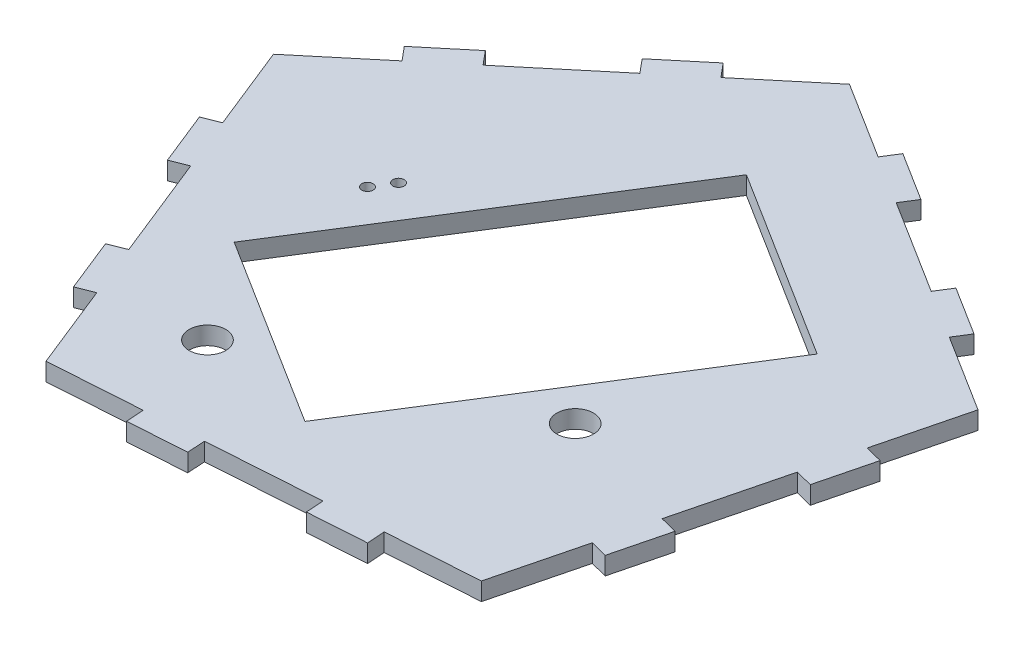
SolidWorks part; units mm, degrees
ref_plane "Front Plane" through (0, 0, 0) normal (0, 0, 1) x (1, 0, 0)
ref_plane "Top Plane" through (0, 0, 0) normal (0, 1, 0) x (1, 0, 0)
ref_plane "Right Plane" through (0, 0, 0) normal (1, 0, 0) x (0, 0, -1)
sketch "Sketch1" plane through (0, 0, 0) normal (0, 1, 0) x (1, 0, 0)
  line L1 (-59.9258, 15.1181) -> (-32.8962, -52.3211)
  line L2 (-32.8962, -52.3211) -> (39.5948, -47.4543)
  line L3 (39.5948, -47.4543) -> (57.3672, 22.9927)
  line L4 (57.3672, 22.9927) -> (-4.14, 61.6646)
  line L5 (-4.14, 61.6646) -> (-59.9258, 15.1181)
  circle A0 centre (0, 0) radius 50 construction
  dimension "D1" = 100
extrude "Boss-Extrude1" add sketch "Sketch1" along normal blind 3.18
ref_axis "Axis" through (0, 3.339, 0) along (0, -1, 0)
sketch "Axis Check" plane through (0, 3.18, 0) normal (0, 1, 0) x (1, 0, 0)
  line L0 (3.3493, -49.8877) -> (-4.14, 61.6646) construction
  line L1 (-32.8962, -52.3211) -> (39.5948, -47.4543) construction
  line L2 (57.3672, 22.9927) -> (-46.411, -18.6015) construction
  line L3 (-59.9258, 15.1181) -> (-32.8962, -52.3211) construction
  line L4 (-32.0329, 38.3913) -> (39.5948, -47.4543) construction
  line L5 (-4.14, 61.6646) -> (-59.9258, 15.1181) construction
  line L6 (-59.9258, 15.1181) -> (48.481, -12.2308) construction
  line L7 (39.5948, -47.4543) -> (57.3672, 22.9927) construction
  line L8 (-32.8962, -52.3211) -> (26.6136, 42.3287) construction
  line L9 (57.3672, 22.9927) -> (-4.14, 61.6646) construction
sketch "Sketch2" plane through (0, 0, 0) normal (0, -1, 0) x (1, 0, 0)
  line L0 (-53.8107, 0.1392) -> (-50.859, -1.0438)
  line L1 (-53.8107, 0.1392) -> (-50.1723, 9.2172)
  line L2 (-50.859, -1.0438) -> (-47.2205, 8.0342)
  line L3 (-50.1723, 9.2172) -> (-47.2205, 8.0342)
  line L4 (-59.9258, -15.1181) -> (-32.8962, 52.3211) construction
  line L5 (-42.6498, 27.9858) -> (-39.0113, 37.0638)
  line L6 (-42.6498, 27.9858) -> (-39.6981, 26.8028)
  line L7 (-39.0113, 37.0638) -> (-36.0596, 35.8808)
  line L8 (-39.6981, 26.8028) -> (-36.0596, 35.8808)
  line L9 (-46.411, 18.6015) -> (-19.2439, 7.7129) construction
  line L10 (-40.8306, 32.5248) -> (-37.8788, 31.3418) construction
  dimension "D1" = 3.18
  dimension "D2" = 9.78
  dimension "D3" = 10.11
extrude "Cut F" [suppressed] cut sketch "Sketch2" against normal through all
sketch "Sketch4" plane through (0, 3.18, 0) normal (0, 1, 0) x (1, 0, 0)
  line L9 (26.6136, 42.3287) -> (-26.6136, -42.3287) construction
  line L10 (57.3672, 22.9927) -> (-4.14, 61.6646) construction
  line L11 (-34.4964, -17.2915) -> (0.6335, 38.5824)
  line L12 (-34.4964, -17.2915) -> (-0.6335, -38.5824)
  line L13 (0.6335, 38.5824) -> (34.4964, 17.2915)
  line L14 (-0.6335, -38.5824) -> (34.4964, 17.2915)
  line L15 (-34.4964, -17.2915) -> (34.4964, 17.2915) construction
  line L16 (0.6335, 38.5824) -> (-0.6335, -38.5824) construction
  line L20 (0, 0) -> (39.0006, -24.5211) construction
  circle A0 centre (-21.8232, -34.7095) radius 3.25
  circle A1 centre (23.7041, -14.9036) radius 3.25
  point P5 (0, 0)
  point P6 (-21.8232, -34.7095)
  dimension "D3" = 6.5
  dimension "D1" = 40
  dimension "D2" = 66
  dimension "D4" = 8
  dimension "D5" = 8
extrude "Top Cut" cut sketch "Sketch4" against normal blind 10
sketch "Sketch7" plane through (0, 3.18, 0) normal (0, 1, 0) x (1, 0, 0)
  line L0 (0, 0) -> (26.6136, 42.3287) construction
  line L1 (57.3672, 22.9927) -> (-4.14, 61.6646) construction
  line L2 (-5.3227, -8.4657) -> (-29.0268, 6.4379) construction
  line L3 (-12.4958, -8.6807) -> (-31.1559, 3.0516) construction
  line L5 (0.6335, 38.5824) -> (-34.4964, -17.2915) construction
  circle A0 centre (-29.0268, 6.4379) radius 1
  circle A1 centre (-31.1559, 3.0516) radius 1
  dimension "D5" = 2
  dimension "D1" = 4
  dimension "D2" = 14
  dimension "D3" = 8
  dimension "D4" = 8
extrude "Top Cut 2" cut sketch "Sketch7" against normal through all
sketch "Sketch8" [suppressed] plane through (0, 3.18, 0) normal (0, 1, 0) x (1, 0, 0)
  line L0 (3.3493, -49.8877) -> (-4.14, 61.6646) construction
  line L5 (-32.8962, -52.3211) -> (39.5948, -47.4543) construction
  line L6 (-17.9455, -31.2723) -> (21.9647, -28.5929)
  line L11 (-17.9455, -31.2723) -> (-21.9647, 28.5929)
  line L12 (21.9647, -28.5929) -> (17.9455, 31.2723)
  line L13 (-21.9647, 28.5929) -> (17.9455, 31.2723)
  point P4 (1.4955, -22.2759)
  dimension "D1" = 60
  dimension "D2" = 40
  dimension "D3" = 20
extrude "Bottom Cut" [suppressed] cut sketch "Sketch8" against normal blind 10
sketch "Sketch9" [suppressed] plane through (0, 3.18, 0) normal (0, 1, 0) x (1, 0, 0)
  line L0 (19.9551, 1.3397) -> (-19.9551, -1.3397) construction
  line L1 (21.9647, -28.5929) -> (17.9455, 31.2723) construction
  line L2 (-21.9647, 28.5929) -> (-17.9455, -31.2723) construction
  line L3 (-19.9551, -1.3397) -> (-44.4689, -2.9855) construction
  line L4 (19.9551, 1.3397) -> (42.6839, 2.8657) construction
  line L5 (-32.8962, -52.3211) -> (39.5948, -47.4543) construction
  line L6 (-29.6051, -6.8886) -> (-32.3788, -7.0748)
  line L7 (-29.6051, -6.8886) -> (-30.2602, 2.8694)
  line L8 (-30.2602, 2.8694) -> (-33.0339, 2.6832)
  line L9 (-32.3788, -7.0748) -> (-33.0339, 2.6832)
  line L10 (-29.6051, -6.8886) -> (-33.0339, 2.6832) construction
  line L11 (-30.2602, 2.8694) -> (-32.3788, -7.0748) construction
  line L12 (33.0339, -2.6832) -> (30.2602, -2.8694)
  line L13 (33.0339, -2.6832) -> (32.3788, 7.0748)
  line L14 (32.3788, 7.0748) -> (29.6051, 6.8886)
  line L15 (30.2602, -2.8694) -> (29.6051, 6.8886)
  line L16 (33.0339, -2.6832) -> (29.6051, 6.8886) construction
  line L17 (32.3788, 7.0748) -> (30.2602, -2.8694) construction
  line L18 (-32.8962, -52.3211) -> (39.5948, -47.4543) construction
  point P6 (-31.3195, -2.1027)
  point P13 (31.3195, 2.1027)
  dimension "D1" = 9.78
  dimension "D4" = 9.78
  dimension "D5" = 10
  dimension "D6" = 10
  dimension "D2" = 2.78
  dimension "D3" = 2.78
extrude "Battery Holder Cut" [suppressed] cut sketch "Sketch9" against normal blind 3.18
sketch "Sketch3" plane through (0, 3.18, 0) normal (0, 1, 0) x (1, 0, 0)
  line L0 (0, 0) -> (-40.9819, 49.1167) construction
  line L1 (-49.5112, 27.9494) -> (-45.4366, 23.066)
  line L3 (-45.4366, 23.066) -> (-37.5894, 29.6135)
  line L4 (-41.664, 34.4969) -> (-37.5894, 29.6135)
  line L5 (-4.14, 61.6646) -> (-59.9258, 15.1181) construction
  line L6 (-71.9961, 5.0469) -> (-69.9588, 2.6052)
  line L7 (-71.9961, 5.0469) -> (-47.4739, 25.5077)
  line L14 (-26.4764, 47.1691) -> (-22.4018, 42.2857)
  line L16 (-22.4018, 42.2857) -> (-14.5546, 48.8333)
  line L17 (-18.6292, 53.7166) -> (-14.5546, 48.8333)
  line L18 (-42.539, 27.5695) -> (-41.513, 26.3398) construction
  line L19 (-49.5112, 27.9494) -> (-41.664, 34.4969)
  line L21 (-26.4764, 47.1691) -> (-18.6292, 53.7166)
  line L22 (-16.5919, 51.275) -> (4.7866, 69.1127)
  line L23 (-39.6267, 32.0552) -> (-24.4391, 44.7274)
  line M18 (-4.14, 61.6646) -> (-59.9258, 15.1181)
  dimension "D1" = 3.18
  dimension "D2" = 10.22
  dimension "D3" = 9.89
  dimension "D4" = 100
extrude "Extrude M" add sketch "Sketch3" against normal up to surface (3.18 mm away) contours L21 L14 L7 L17 | L19 L1 L4 M18 region at (-44.5689, 3.18, -30.0023) region at (-21.5341, 3.18, -49.222) up to face at (-29.0268, 0, -5.4379)
pattern_circular "Circle F" [suppressed] count 5 over 360 about axis through (0, 3.339, 0) along (0, -1, 0) of bodies 173
pattern_circular "Circle M" count 5 over 360 about axis through (0, 3.339, 0) along (0, -1, 0) of "Extrude M"
pattern_circular "Circle Side F" [suppressed] count 5 over 360 about axis through (0, 3.339, 0) along (0, -1, 0) of bodies 173
pattern_circular "Circle Side M" [suppressed] count 5 over 360 about axis through (0, 3.339, 0) along (0, -1, 0) of bodies 168
equation "\"kerf\"= .22mm"
equation "\"tabWidthF\"= 10 - \"kerf\""
equation "\"tabThickness\"= 3.18"
equation "\"D1@Sketch2\"=\"tabThickness\""
equation "\"tabWidthM\"= 10 + \"kerf\""
equation "\"halfkerf\"= \"kerf\" / 2.00mm"
equation "\"D1@Sketch9\"=\"tabWidthF\""
equation "\"D4@Sketch9\"=\"tabWidthF\""
equation "\"D1@Battery Holder Cut\" = \"tabThickness\""
equation "\"tabLength\" = \"kerf\" + 12"
